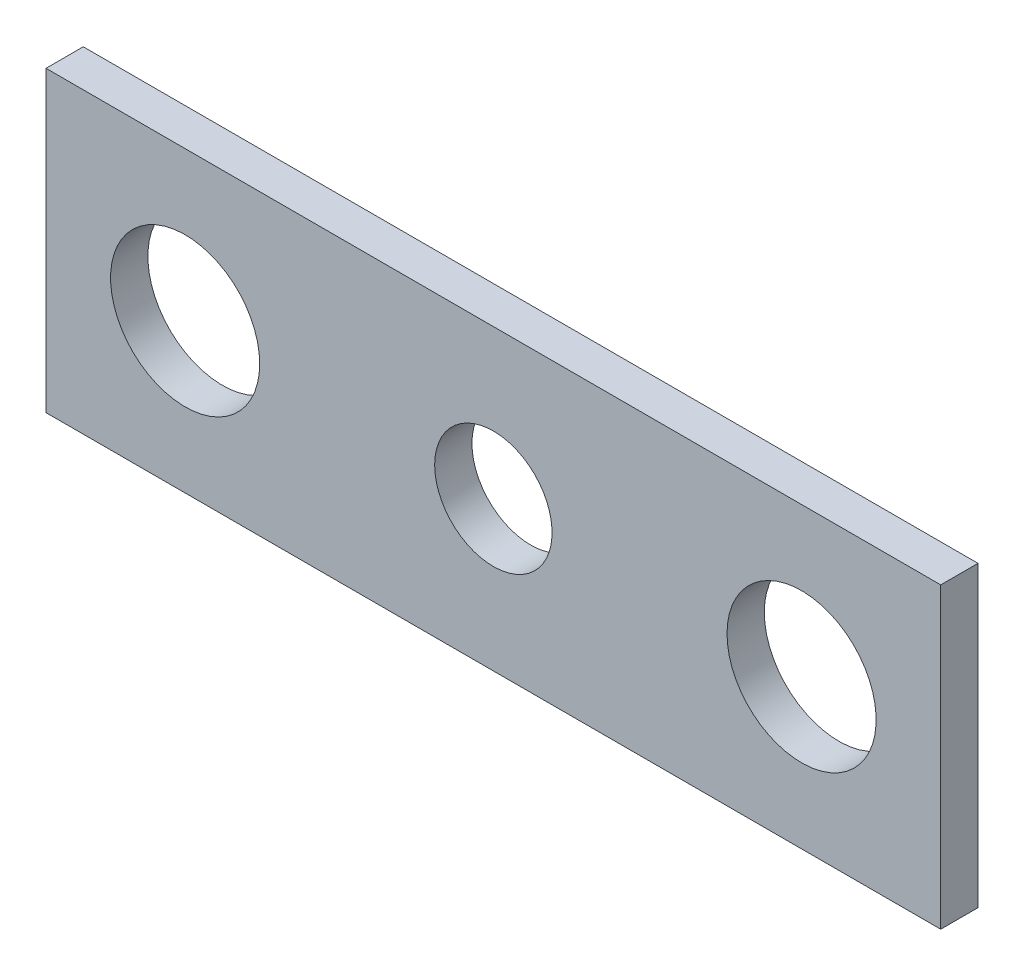
SolidWorks part; units mm, degrees
ref_plane "Front Plane" through (0, 0, 0) normal (0, 0, 1) x (1, 0, 0)
ref_plane "Top Plane" through (0, 0, 0) normal (0, 1, 0) x (1, 0, 0)
ref_plane "Right Plane" through (0, 0, 0) normal (1, 0, 0) x (0, 0, -1)
sketch "Sketch1" plane through (0, 0, 0) normal (0, 0, 1) x (1, 0, 0)
  line L1 (0, 0) -> (-152.4, 0)
  line L2 (0, 0) -> (0, 50.8)
  line L3 (0, 50.8) -> (-152.4, 50.8)
  line L4 (-152.4, 0) -> (-152.4, 50.8)
  dimension "D1" = 50.8
  dimension "D2" = 152.4
extrude "Boss-Extrude1" add sketch "Sketch1" along normal blind 6.35
sketch "Sketch2" plane through (0, 0, 0) normal (0, 0, -1) x (-1, 0, 0)
  line L0 (76.2, 54.4848) -> (76.2, 3.6848) construction
  line L3 (152.4, 0) -> (0, 0) construction
  line L4 (0, 50.8) -> (152.4, 50.8) construction
  circle A0 centre (23.7, 25.4) radius 12.7
  circle A1 centre (76.2, 25.4) radius 10
  circle A2 centre (128.7, 25.4) radius 12.7
  point P5 (63.5, 21.7152)
  point P13 (76.2, 50.8)
  dimension "D1" = 25.4
  dimension "D2" = 20
  dimension "D3" = 52.5
  dimension "D4" = 25.4
extrude "Cut-Extrude1" cut sketch "Sketch2" against normal blind 6.35 contours A0 | A1 | A2
